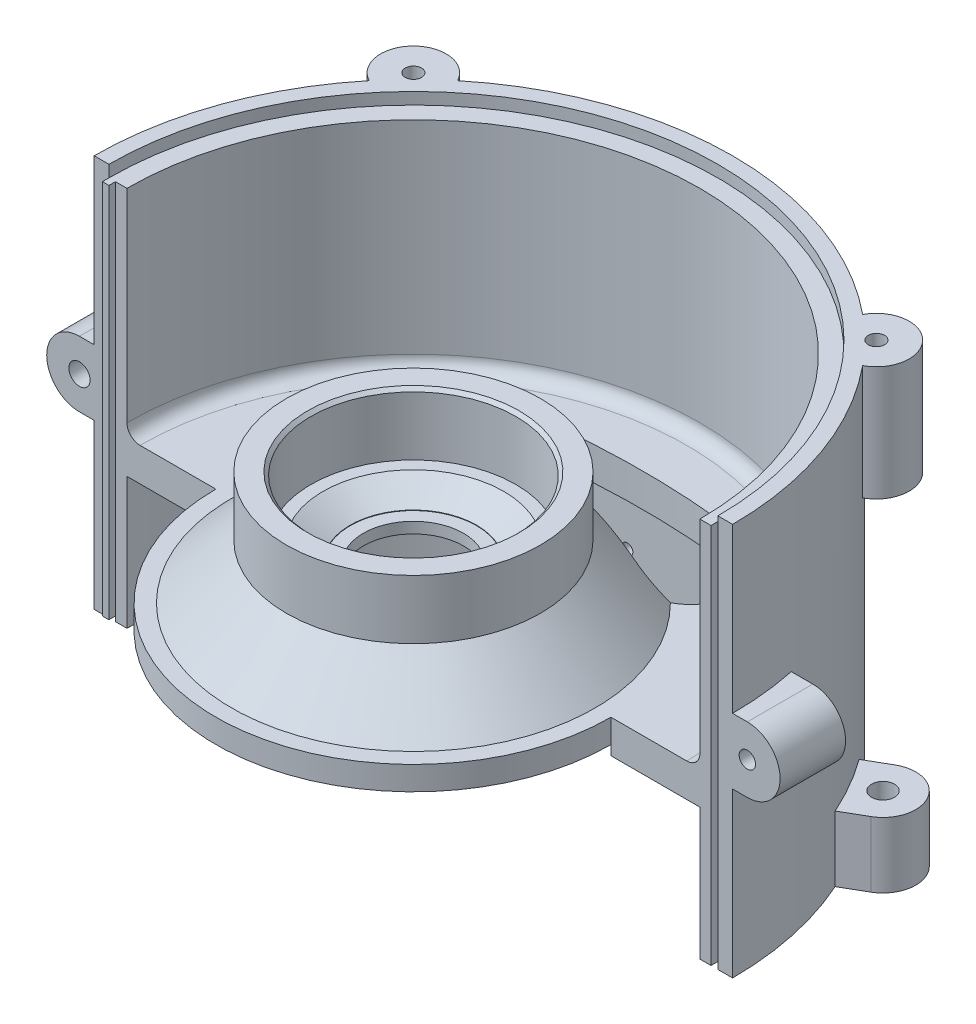
SolidWorks part; units mm, degrees
ref_plane "Plano frontal" through (0, 0, 0) normal (0, 0, 1) x (1, 0, 0)
ref_plane "Plano superior" through (0, 0, 0) normal (0, 1, 0) x (1, 0, 0)
ref_plane "Plano direito" through (0, 0, 0) normal (1, 0, 0) x (0, 0, -1)
sketch "Esboço3" plane through (0, 0, 0) normal (0, 0, 1) x (1, 0, 0)
  line L2 (97.5, 79.8) -> (97.5, 11.3045)
  line L4 (87.5, 0) -> (60.3424, 0)
  line L5 (31.3, 25.96) -> (27.6265, 25.96)
  line L6 (60.3424, 0) -> (60.3424, 2.95)
  line L7 (60.3424, 2.95) -> (52, 2.95)
  line L8 (52, 2.95) -> (44, 10.95)
  line L9 (44, 10.95) -> (31, 10.95)
  line L10 (31, 10.95) -> (31, 13.7)
  line L11 (31, 13.7) -> (22.6, 13.7)
  line L12 (22.6, 13.7) -> (22.6, 17)
  line L13 (22.6, 17) -> (19.3, 17)
  line L14 (19.3, 17) -> (19.3, 17.7)
  line L15 (19.3, 17.7) -> (15.3, 17.7)
  line L16 (15.3, 17.7) -> (15.3, 21.05)
  line L17 (15.3, 21.05) -> (19.3, 21.05)
  line L18 (97.5, 79.8) -> (93, 79.8)
  line L19 (93, 79.8) -> (93, 76.2)
  line L20 (93, 76.2) -> (87.5, 76.2)
  line L21 (87.5, 76.2) -> (87.5, 14.2)
  line L22 (83.5, 10.2) -> (55.5, 10.2)
  line L23 (55.5, 10.2) -> (38.8, 26.9)
  line L24 (38.8, 26.9) -> (38.8, 44.96)
  line L25 (38.8, 44.96) -> (32.3, 44.96)
  line L26 (32.3, 44.96) -> (31.3, 43.96)
  line L27 (31.3, 43.96) -> (31.3, 25.96)
  line L29 (19.3, 21.05) -> (19.3, 21.2)
  line L30 (55, 0) -> (-55, 0) construction
  line L31 (27.6265, 25.96) -> (19.3, 21.2)
  line L33 (97.5, 0) -> (97.5, 11.3045)
  line L34 (97.5, 0) -> (97.5, -40.2)
  line L35 (97.5, -40.2) -> (87.5, -40.2)
  line L36 (87.5, -40.2) -> (87.5, 0)
  arc A1 (87.5, 14.2) -> (83.5, 10.2) centre (83.5, 14.2) cw
  dimension "D32" = 79.8
  dimension "D2" = 7.5
  dimension "D3" = 135
  dimension "D4" = 19
  dimension "D5" = 120
  dimension "D6" = 0.15
  dimension "D7" = 135
  dimension "D8" = 16
  dimension "D9" = 34.84
  dimension "D10" = 28
  dimension "D11" = 66
  dimension "D12" = 3.6
  dimension "D13" = 93
  dimension "D14" = 10
  dimension "D15" = 17.7
  dimension "D16" = 1
  dimension "D17" = 31.3
  dimension "D18" = 10
  dimension "D19" = 52
  dimension "D20" = 44
  dimension "D21" = 135
  dimension "D22" = 31
  dimension "D23" = 22.6
  dimension "D24" = 19.3
  dimension "D25" = 15.3
  dimension "D26" = 2.75
  dimension "D27" = 3.3
  dimension "D28" = 0.7
  dimension "D29" = 3.35
  dimension "D31" = 97.5
ref_axis "Eixo1" through (0, -3.3221, 0) along (0, 1, 0)
revolve "Revolução2" add sketch "Esboço3" angle 180 about axis through (0, -3.3221, 0) along (0, 1, 0)
sketch "Esboço20" plane through (0, 0, 0) normal (0, 0, 1) x (1, 0, 0)
  line L0 (60.3424, 2.95) -> (60.3424, 10.2)
  line L1 (83.5, 10.2) -> (-83.5, 10.2) construction
  line L2 (60.3424, 10.2) -> (55.5, 10.2)
  line L3 (83.5, 10.2) -> (55.5, 10.2) construction
  line L4 (55.5, 10.2) -> (38.8, 26.9)
  line L5 (38.8, 26.9) -> (38.8, 44.96)
  line L6 (38.8, 44.96) -> (32.3, 44.96) construction
  line L7 (38.8, 44.96) -> (32.3, 44.96)
  line L8 (32.3, 44.96) -> (-32.3, 44.96) construction
  line L9 (32.3, 44.96) -> (31.3, 43.96)
  line L10 (31.3, 43.96) -> (31.3, 25.96)
  line L11 (31.3, 25.96) -> (27.6265, 25.96)
  line L12 (31.3, 25.96) -> (-31.3, 25.96) construction
  line L13 (27.6265, 25.96) -> (19.3, 21.2) construction
  line L14 (27.6265, 25.96) -> (19.3, 21.2)
  line L15 (19.3, 21.2) -> (19.3, 21.05)
  line L16 (19.3, 21.05) -> (15.3, 21.05)
  line L17 (15.3, 21.05) -> (15.3, 17.7)
  line L18 (15.3, 17.7) -> (19.3, 17.7)
  line L19 (19.3, 17.7) -> (19.3, 17)
  line L20 (19.3, 17) -> (22.6, 17)
  line L21 (22.6, 17) -> (22.6, 13.7)
  line L22 (22.6, 13.7) -> (31, 13.7)
  line L23 (31, 13.7) -> (31, 10.95)
  line L24 (31, 10.95) -> (44, 10.95)
  line L25 (44, 10.95) -> (52, 2.95)
  line L26 (52, 2.95) -> (60.3424, 2.95)
revolve "Revolução3" add sketch "Esboço20" angle 360 about axis through (0, -3.3221, 0) along (0, 1, 0)
sketch "Esboço4" plane through (0, 79.8, 0) normal (0, 1, 0) x (1, 0, 0)
  line L0 (70.71, 70.71) -> (-70.71, 70.71) construction
  line L1 (-70.71, 70.71) -> (-70.71, -70.71) construction
  line L2 (-70.71, -70.71) -> (70.71, -70.71) construction
  line L3 (70.71, -70.71) -> (70.71, 70.71) construction
  line L4 (-66, 0) -> (66, 0) construction
  line L5 (0, -66) -> (0, 66) construction
  circle A0 centre (70.71, 70.71) radius 10
  circle A3 centre (-70.71, 70.71) radius 10
  point P0 (70.71, 0)
  point P8 (0, -70.71)
  dimension "D2" = 20
  dimension "D1" = 141.42
extrude "Ressalto-extrusão1" add sketch "Esboço4" against normal blind 35
sketch "Esboço5" plane through (0, -40.2, 0) normal (0, -1, 0) x (1, 0, 0)
  line L0 (0, 0) -> (70.71, -70.71) construction
  line L1 (0, 0) -> (0, -105) construction
  line L2 (10, -105) -> (10, -96.9858)
  line L3 (-10, -105) -> (-10, -96.9858)
  line L4 (10, -96.9858) -> (-10, -96.9858)
  arc A1 (10, -105) -> (-10, -105) centre (0, -105) cw
  arc A3 (-97.5, 0) -> (97.5, 0) centre (0, 0) ccw construction
  dimension "D2" = 10
  dimension "D1" = 105
extrude "Ressalto-extrusão2" add sketch "Esboço5" against normal blind 20
sketch "Esboço8" plane through (0, -40.2, 0) normal (0, -1, 0) x (1, 0, 0)
  circle A0 centre (0, -105) radius 3.5
  dimension "D1" = 7
extrude "Corte-extrusão2" cut sketch "Esboço8" against normal blind 20
pattern_circular "PadrãoCircular1" count 6 over 360 about axis through (0, 0, 0) along (0, 1, 0) of "Ressalto-extrusão2", "Corte-extrusão2"
sketch "Esboço6" plane through (0, 79.8, 0) normal (0, 1, 0) x (1, 0, 0)
  circle A2 centre (70.71, 70.71) radius 2.5
  circle A3 centre (-70.71, 70.71) radius 2.5
  dimension "D1" = 5
extrude "Corte-extrusão1" cut sketch "Esboço6" against normal blind 15
sketch "Esboço9" plane through (0, 13.7, 0) normal (0, -1, 0) x (1, 0, 0)
  line L0 (0, 0) -> (18.7383, -18.7383) construction
  line L1 (-18.7383, -18.7383) -> (0, 0) construction
  line L2 (-18.7383, -18.7383) -> (18.7383, -18.7383) construction
  circle A2 centre (18.7383, -18.7383) radius 1.25
  circle A3 centre (-18.7383, -18.7383) radius 1.25
  circle A4 centre (-18.7383, 18.7383) radius 1.25
  circle A5 centre (18.7383, 18.7383) radius 1.25
  point P8 (0, 0)
  point P13 (4.0879, -3.0957)
  dimension "D2" = 26.5
  dimension "D1" = 26.5
  dimension "D3" = 2
extrude "Corte-extrusão3" cut sketch "Esboço9" against normal blind 6
sketch "Esboço10" plane through (0, 0, 0) normal (0, 0, 1) x (1, 0, 0)
  line L0 (93.1, -40.2) -> (93.1, 76.2)
  line L1 (93.1, 76.2) -> (93, 76.2) construction
  line L2 (91, 76.2) -> (90.9, 76.2) construction
  line L3 (93.1, 76.2) -> (90.9, 76.2)
  line L5 (90.9, 76.2) -> (90.9, -40.2)
  line L6 (90.9, -40.2) -> (93.1, -40.2)
  line L7 (87.5, -40.2) -> (97.5, -40.2) construction
  dimension "D2" = 2
  dimension "D3" = 0.1
extrude "Corte-extrusão4" cut sketch "Esboço10" against normal blind 3.5
sketch "Esboço11" plane through (0, 0, 0) normal (0, 0, 1) x (1, 0, 0)
  line L0 (-91, -38.7) -> (-91, 76.2)
  line L1 (-87.5, -40.2) -> (-97.5, -40.2) construction
  line L3 (-91, 76.2) -> (-93, 76.2)
  line L4 (-93, 76.2) -> (-93, -38.7)
  line L5 (-93, -38.7) -> (-91, -38.7)
  line L6 (-93, 79.8) -> (-93, 76.2) construction
  line L7 (-93, 76.2) -> (-87.5, 76.2) construction
  dimension "D1" = 2
  dimension "D2" = 1.5
extrude "Ressalto-extrusão5" add sketch "Esboço11" along normal blind 2
sketch "Esboço12" plane through (0, 0, 0) normal (0, 0, 1) x (1, 0, 0)
  line L0 (-124.1305, 19.8) -> (136.9824, 19.8) construction
  line L1 (-97.5, -40.2) -> (-97.5, 79.8) construction
  line L2 (-97.5, -40.2) -> (-97.5, 79.8) construction
  line L3 (-102, 9.8) -> (-102, 29.8) construction
  line L4 (-102, 29.8) -> (-87.5, 29.8)
  line L5 (-87.5, 76.2) -> (-87.5, 14.2) construction
  line L6 (-87.5, 29.8) -> (-87.5, 9.8)
  line L7 (-87.5, 9.8) -> (-102, 9.8)
  arc A1 (-102, 9.8) -> (-102, 29.8) centre (-102, 19.8) cw
  circle A2 centre (-102, 19.8) radius 3.25
  point P8 (-97.5, 19.8)
  dimension "D2" = 6.5
  dimension "D1" = 20
  dimension "D3" = 4.5
extrude "Ressalto-extrusão6" add sketch "Esboço12" against normal blind 20
sketch "Esboço13" plane through (0, 0, 0) normal (0, 0, 1) x (1, 0, 0)
  line L0 (102, 29.8) -> (102, 9.8) construction
  line L3 (-102, 19.8) -> (140.3594, 19.8) construction
  line L4 (102, 29.8) -> (93.1, 29.8)
  line L5 (93.1, 29.8) -> (93.1, 9.8)
  line L6 (93.1, 9.8) -> (102, 9.8)
  line L7 (93.1, -40.2) -> (93.1, 76.2) construction
  line L8 (97.5, -40.2) -> (97.5, 79.8) construction
  arc A0 (102, 9.8) -> (102, 29.8) centre (102, 19.8) ccw
  circle A1 centre (102, 19.8) radius 2.5
  dimension "D3" = 5
  dimension "D1" = 20
  dimension "D2" = 4.5
extrude "Ressalto-extrusão7" add sketch "Esboço13" against normal blind 20
sketch "Esboço14" plane through (0, 0, 0) normal (0, -1, 0) x (-1, 0, 0)
  line L0 (0, -185) -> (0, 115) construction
  arc A0 (32.1753, 52.6546) -> (-32.1753, 52.6546) centre (0, -166.8724) ccw construction
  arc A1 (34.3505, 67.4961) -> (-34.3505, 67.4961) centre (0, -166.8724) ccw
  arc A2 (30, 37.8132) -> (-30, 37.8132) centre (0, -166.8724) ccw
  arc A3 (30, 37.8132) -> (34.3505, 67.4961) centre (32.1753, 52.6546) ccw
  arc A4 (-34.3505, 67.4961) -> (-30, 37.8132) centre (-32.1753, 52.6546) ccw
  arc A5 (10, 105) -> (-10, 105) centre (0, 105) ccw construction
  point P3 (0, 55)
  dimension "D1" = 30
  dimension "D2" = 300
  dimension "D3" = 55
  dimension "D4" = 60
extrude "Corte-extrusão5" cut sketch "Esboço14" against normal through all
sketch "Esboço16" plane through (0, 76.2, 0) normal (0, 1, 0) x (1, 0, 0)
  circle A0 centre (0, 0) radius 93
extrude "Corte-extrusão6" cut sketch "Esboço16" along normal blind 10
sketch "Esboço17" plane through (0, -40.2, 0) normal (0, -1, 0) x (1, 0, 0)
  circle A0 centre (0, 0) radius 92.9674
  circle A1 centre (0, 0) radius 90.9674
  dimension "D1" = 2
extrude "Corte-extrusão7" cut sketch "Esboço17" against normal blind 1.5
ref_plane "Plano1" through (0, -20.1, 0) normal (0, -1, 0) x (-1, 0, 0)
sketch "Esboço18" plane through (0, -20.1, 0) normal (0, -1, 0) x (-1, 0, 0)
  line L0 (0, 0) -> (0, 115) construction
  line L1 (50, 81.2817) -> (-50, 81.2817)
  line L2 (50, 81.2817) -> (50, 64.043)
  line L3 (50, 64.043) -> (-50, 64.043)
  line L4 (-50, 81.2817) -> (-50, 64.043)
  line L5 (50, 81.2817) -> (-50, 64.043) construction
  line L6 (50, 64.043) -> (-50, 81.2817) construction
  arc A0 (10, 105) -> (-10, 105) centre (0, 105) ccw construction
  point P0 (0, 72.6623)
  dimension "D1" = 100
extrude "Corte-extrusão8" cut sketch "Esboço18" against normal mid plane 30
sketch "Esboço19" plane through (0, -20.1, 0) normal (0, -1, 0) x (-1, 0, 0)
  line L0 (32.3966, 81.2817) -> (-32.3966, 81.2817)
  arc A0 (32.3966, 81.2817) -> (-32.3966, 81.2817) centre (0, 0) ccw
  arc A1 (87.5, 0) -> (-87.5, 0) centre (0, 0) ccw construction
extrude "Ressalto-extrusão9" add sketch "Esboço19" along normal mid plane 30
sketch "Esboço22" plane through (0, 0, -81.2817) normal (0, 0, 1) x (1, 0, 0)
  line L0 (50, -24.1) -> (-50, -24.1) construction
  line L1 (50, -35.1) -> (50, -5.1) construction
  line L2 (-50, -5.1) -> (-50, -35.1) construction
  line L3 (-32.3966, -35.1) -> (32.3966, -35.1) construction
  line L4 (-15.9, -24.1) -> (-15.9, -18.2226) construction
  line L5 (-15.9, -18.2226) -> (15.9, -18.2226) construction
  line L6 (15.9, -18.2226) -> (15.9, -24.1) construction
  circle A0 centre (-15.9, -24.1) radius 1.65
  circle A1 centre (15.9, -24.1) radius 1.65
  point P13 (0, -18.2226)
  point P14 (0, -24.1)
  dimension "D2" = 3.3
  dimension "D3" = 31.8
  dimension "D1" = 11
extrude "Corte-extrusão9" cut sketch "Esboço22" against normal blind 10
